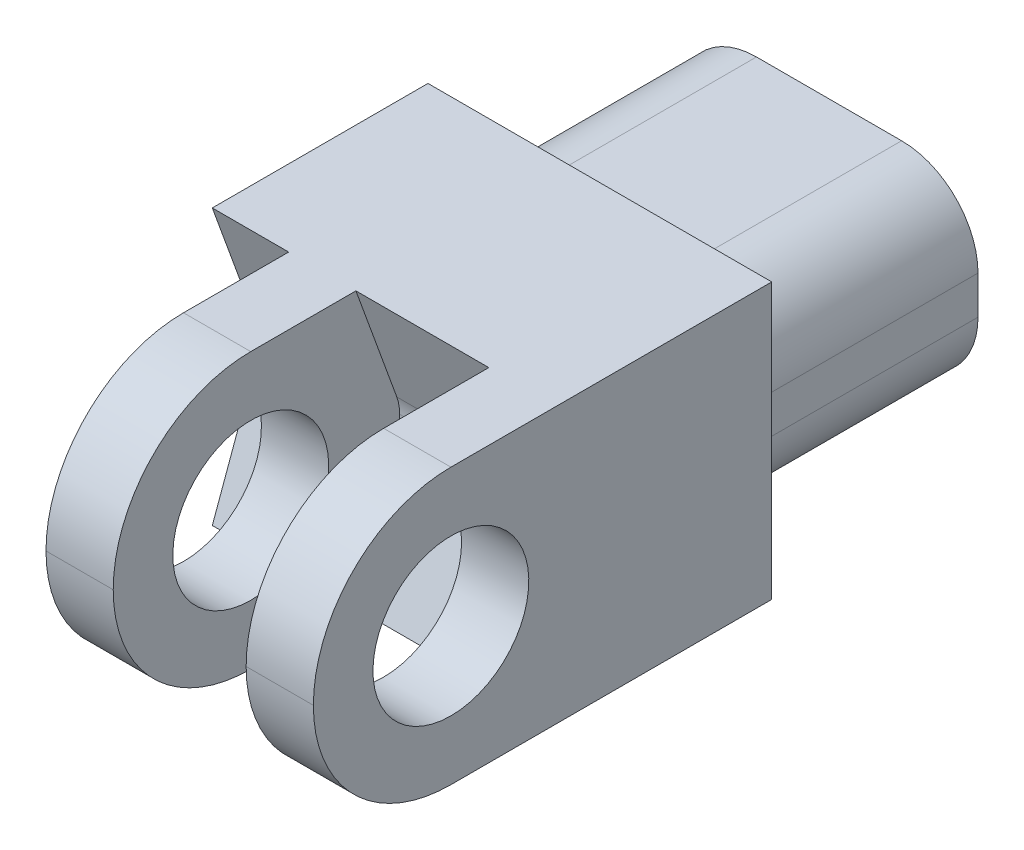
SolidWorks part; units mm, degrees
ref_plane "Plan de face" through (0, 0, 0) normal (0, 0, 1) x (1, 0, 0)
ref_plane "Plan de dessus" through (0, 0, 0) normal (0, 1, 0) x (1, 0, 0)
ref_plane "Plan de droite" through (0, 0, 0) normal (1, 0, 0) x (0, 0, -1)
sketch "Sketch2" plane through (0, 0, 0) normal (0, 0, 1) x (1, 0, 0)
  line L1 (12.3825, -7.9375) -> (-12.3825, -7.9375)
  line L2 (12.3825, -7.9375) -> (12.3825, 7.9375)
  line L3 (12.3825, 7.9375) -> (-12.3825, 7.9375)
  line L4 (-12.3825, -7.9375) -> (-12.3825, 7.9375)
  line L5 (12.3825, -7.9375) -> (-12.3825, 7.9375) construction
  line L6 (12.3825, 7.9375) -> (-12.3825, -7.9375) construction
  point P0 (0, 0)
  dimension "D1" = 24.765
  dimension "D2" = 15.875
extrude "Boss-Extrude1" add sketch "Sketch2" against normal blind 19.05
sketch "Sketch3" plane through (0, 0, 0) normal (0, 0, 1) x (1, 0, 0)
  line L1 (14.2875, -11.43) -> (-14.2875, -11.43)
  line L2 (14.2875, -11.43) -> (14.2875, 11.43)
  line L3 (14.2875, 11.43) -> (-14.2875, 11.43)
  line L4 (-14.2875, -11.43) -> (-14.2875, 11.43)
  line L5 (14.2875, -11.43) -> (-14.2875, 11.43) construction
  line L6 (14.2875, 11.43) -> (-14.2875, -11.43) construction
  point P0 (0, 0)
  dimension "D1" = 28.575
  dimension "D2" = 22.86
extrude "Boss-Extrude2" add sketch "Sketch3" along normal blind 38.1
sketch "Sketch4" plane through (0, -11.43, 0) normal (0, -1, 0) x (-1, 0, 0)
  line L0 (14.2875, -38.1) -> (-14.2875, -38.1) construction
  line L1 (14.2875, -38.1) -> (7.9375, -38.1)
  line L2 (14.2875, -38.1) -> (14.2875, -14.2875)
  line L3 (14.2875, -14.2875) -> (7.9375, -14.2875)
  line L4 (7.9375, -38.1) -> (7.9375, -14.2875)
  line L5 (2.3495, -38.1) -> (-8.6995, -38.1)
  line L6 (2.3495, -38.1) -> (2.3495, -14.2875)
  line L7 (2.3495, -14.2875) -> (-8.6995, -14.2875)
  line L8 (-8.6995, -38.1) -> (-8.6995, -14.2875)
  line L9 (-14.2875, -38.1) -> (-14.2875, 0) construction
  dimension "D1" = 23.8125
  dimension "D2" = 23.8125
  dimension "D3" = 6.35
  dimension "D4" = 5.588
  dimension "D5" = 5.588
extrude "Cut-Extrude1" cut sketch "Sketch4" against normal through all
fillet "Fillet5" radius 11.43 4 edges at (-5.1435, -11.43, 38.1) (-5.1435, 11.43, 38.1) (11.4935, 11.43, 38.1) (11.4935, -11.43, 38.1)
sketch "Sketch7" plane through (-7.9375, 0, 0) normal (-1, 0, 0) x (0, 0, 1)
  circle A1 centre (26.67, 0) radius 6.477
  dimension "D1" = 12.954
extrude "Cut-Extrude3" cut sketch "Sketch7" against normal through all
fillet "Fillet3" radius 6.35 4 edges at (-12.3825, -7.9375, -9.525) (-12.3825, 7.9375, -9.525) (12.3825, -7.9375, -9.525) (12.3825, 7.9375, -9.525)
sketch "Esquisse1" plane through (-14.2875, 0, 0) normal (-1, 0, 0) x (0, 0, 1)
  line L0 (14.2875, 11.43) -> (17.9272, 11.43)
  line L1 (14.2875, 11.43) -> (26.67, 11.43) construction
  line L2 (17.9272, 11.43) -> (14.2875, 1.43)
  line L3 (14.2875, 11.43) -> (14.2875, -11.43) construction
  line L4 (14.2875, 1.43) -> (14.2875, 11.43)
  dimension "D1" = 10
  dimension "D2" = 20
extrude "Boss.-Extru.1" add sketch "Esquisse1" against normal up to surface (28.575 mm away) up to face at (14.2875, -6.477, 26.67)
mirror "Symétrie1" about plane through (0, 0, 0) normal (0, 1, 0) of "Boss.-Extru.1"
fillet "Congé3" radius 4 4 edges at (3.175, -1.43, 14.2875) (3.175, 1.43, 14.2875) (-11.1125, -1.43, 14.2875) (-11.1125, 1.43, 14.2875)
